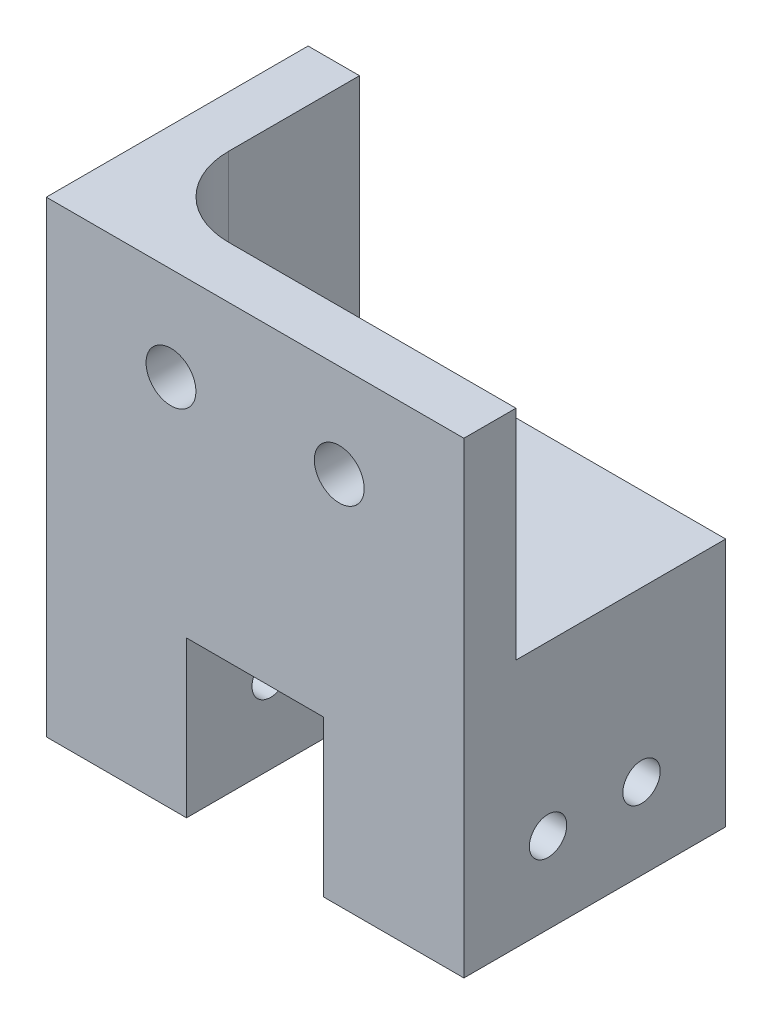
SolidWorks part; units mm, degrees
material "6061 Legierung"
ref_plane "Ebene vorne" through (0, 0, 0) normal (0, 0, 1) x (1, 0, 0)
ref_plane "Ebene oben" through (0, 0, 0) normal (0, 1, 0) x (1, 0, 0)
ref_plane "Ebene rechts" through (0, 0, 0) normal (1, 0, 0) x (0, 0, -1)
sketch "Skizze1" plane through (0, 0, 0) normal (0, 0, 1) x (1, 0, 0)
  line L13 (-11, 155) -> (11, 155)
  line L15 (11, 155) -> (11, 130)
  line L17 (11, 130) -> (33.5, 130)
  line L18 (33.5, 130) -> (33.5, 205)
  line L19 (33.5, 205) -> (-33.5, 205)
  line L23 (-33.5, 130) -> (-33.5, 205)
  line L24 (-11, 130) -> (-33.5, 130)
  line L25 (-11, 155) -> (-11, 130)
  point P16 (0, 205)
  point P19 (0, 155)
sketch "Skizze3" plane through (0, 0, 0) normal (0, 0, 1) x (1, 0, 0)
  line L9 (0, 205) -> (33.5, 205)
  line L10 (33.5, 205) -> (33.5, 130)
  line L11 (33.5, 130) -> (11, 130)
  line L12 (11, 130) -> (11, 155)
  line L13 (11, 155) -> (0, 155)
  line L14 (0, 205) -> (-33.5, 205)
  line L15 (-33.5, 205) -> (-33.5, 130)
  line L16 (-33.5, 130) -> (-11, 130)
  line L17 (-11, 130) -> (-11, 155)
  line L18 (-11, 155) -> (0, 155)
sketch "Skizze4" plane through (0, 0, 0) normal (1, 0, 0) x (0, 0, -1)
  line L0 (15, 0) -> (-15, 0)
  point P8 (0, 0)
extrude "Aufsatz-Linear austragen1" add sketch "Skizze3" along normal blind 21 and the other way blind 21
sketch "Skizze5" plane through (0, 0, 0) normal (0, 1, 0) x (1, 0, 0)
  line L1 (-12.6, 12.65) -> (25.15, 12.65)
  line L2 (25.15, 12.65) -> (25.15, -12.65)
  line L3 (25.15, -12.65) -> (-12.6, -12.65)
  line L5 (-12.6, 10.85) -> (23.35, 10.85)
  line L6 (23.35, 10.85) -> (23.35, -10.85)
  line L7 (23.35, -10.85) -> (-12.6, -10.85)
  arc A0 (-12.6, 12.65) -> (-12.6, -12.65) centre (-12.6, 0) ccw
  arc A1 (-12.6, 10.85) -> (-12.6, -10.85) centre (-12.6, 0) ccw
sketch "Skizze6" plane through (0, 205, 0) normal (0, 1, 0) x (1, 0, 0)
  line L0 (-25.25, 0) -> (-25.25, 21)
  line L1 (33.5, 21) -> (-33.5, 21) construction
  line L2 (-25.25, 21) -> (33.5, 21)
  line L3 (33.5, 21) -> (33.5, -21) construction
  line L4 (33.5, 21) -> (33.5, -12.65)
  line L5 (33.5, -12.65) -> (-12.6, -12.65)
  arc A0 (-12.6, 12.65) -> (-12.6, -12.65) centre (-12.6, 0) ccw construction
  arc A1 (-25.25, 0) -> (-12.6, -12.65) centre (-12.6, 0) ccw
sketch "StingHeigtPos" plane through (0, 0, 0) normal (0, 0, 1) x (1, 0, 0)
  line L0 (0, 170) -> (0, 640)
extrude "Schnitt-Linear austragen1" cut sketch "Skizze6" against normal up to vertex (35 mm away) up to point (0, 170, 0)
sketch "Holes" plane through (0, 0, 0) normal (0, 0, 1) x (1, 0, 0)
  circle A0 centre (13.5, 190) radius 4
  circle A1 centre (-13.5, 190) radius 4
sketch "Skizze9" plane through (0, 0, 0) normal (0, 0, 1) x (1, 0, 0)
  circle A0 centre (-13.5, 190) radius 4
  circle A1 centre (13.5, 190) radius 4
extrude "Schnitt-Linear austragen2" cut sketch "Skizze9" along normal up to surface (21 mm away) up to face at (0, 155, 21)
sketch "Skizze10" plane through (0, 0, 0) normal (1, 0, 0) x (0, 0, -1)
  line L2 (0, 90) -> (21.451, 90) construction
  circle A0 centre (7.5, 37) radius 3
  circle A1 centre (-7.5, 37) radius 3
  circle A4 centre (-7.5, 143) radius 3
  circle A5 centre (7.5, 143) radius 3
sketch "Skizze11" plane through (0, 0, 0) normal (1, 0, 0) x (0, 0, -1)
  circle A0 centre (7.5, 143) radius 3
  circle A1 centre (-7.5, 143) radius 3
extrude "Schnitt-Linear austragen3" cut sketch "Skizze11" against normal up to surface and the other way up to surface up to face at (-33.5, 167.5, 0) other way up to face at (33.5, 168.3333, 4.2167)
